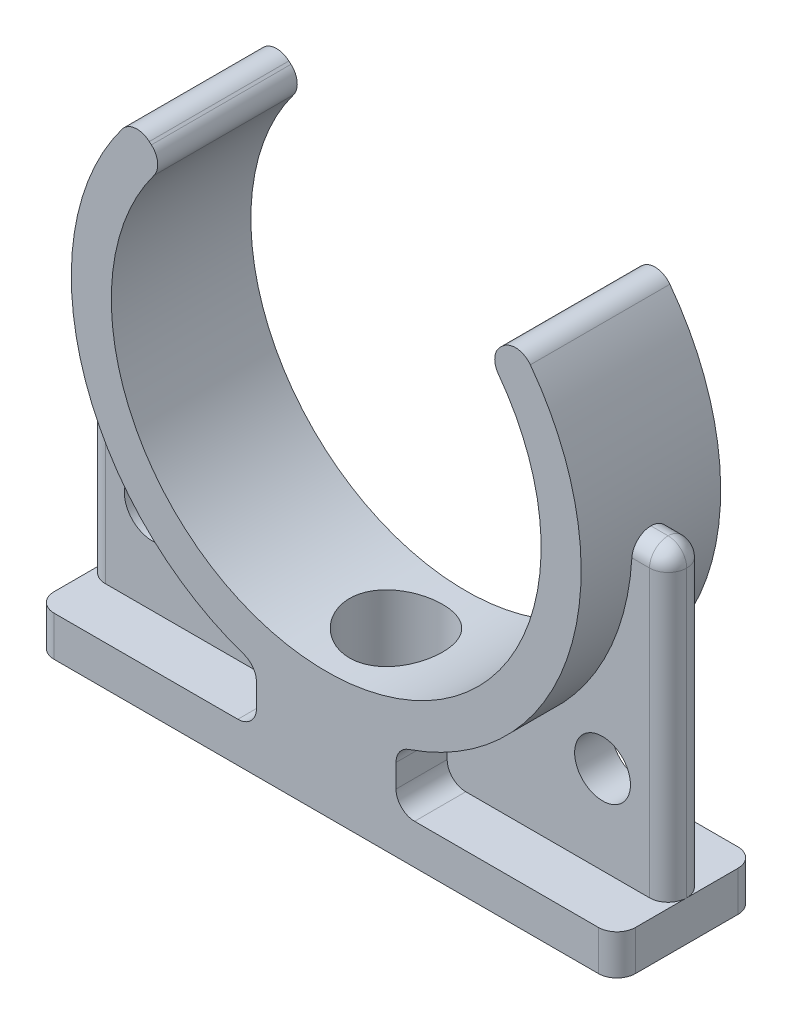
SolidWorks part; units mm, degrees
material "Delrin 2700 NC010, Low Viscosity Acetal Copolymer (SS)"
ref_plane "Front Plane" through (0, 0, 0) normal (0, 0, 1) x (1, 0, 0)
ref_plane "Top Plane" through (0, 0, 0) normal (0, 1, 0) x (1, 0, 0)
ref_plane "Right Plane" through (0, 0, 0) normal (1, 0, 0) x (0, 0, -1)
sketch "Sketch1" plane through (0, 0, 0) normal (0, 0, 1) x (1, 0, 0)
  line L0 (39.6875, 17.145) -> (39.6875, 0) construction
  line L1 (0, 0) -> (79.375, 0)
  line L2 (0, 0) -> (0, 46.99)
  line L3 (0, 46.99) -> (4.8932, 46.99)
  line L4 (79.375, 0) -> (79.375, 46.99)
  line L5 (0, 5.461) -> (30.1625, 5.461)
  line L6 (30.1625, 13.013) -> (30.1625, 5.461)
  line L7 (49.2125, 13.013) -> (49.2125, 5.461)
  line L8 (74.4818, 46.99) -> (79.375, 46.99)
  line L9 (49.2125, 5.461) -> (79.375, 5.461)
  line L10 (13.5513, 69.4559) -> (17.653, 65.8505)
  line L11 (65.8237, 69.4559) -> (61.722, 65.8505)
  circle A0 centre (8.9535, 17.526) radius 3.81
  circle A1 centre (70.4215, 17.526) radius 3.81
  arc A2 (17.653, 65.8505) -> (61.722, 65.8505) centre (39.6875, 46.482) ccw
  arc A3 (49.2125, 13.013) -> (65.8237, 69.4559) centre (39.6875, 46.482) ccw
  arc A4 (13.5513, 69.4559) -> (30.1625, 13.013) centre (39.6875, 46.482) ccw
  point P12 (0, 0)
  point P14 (10.3505, 46.482)
  point P15 (4.8895, 46.482)
  point P16 (39.6875, 17.145)
  point P17 (8.9535, 13.716)
  point P27 (17.653, 65.8505)
  point P28 (61.722, 65.8505)
  dimension "D3" = 61.468
  dimension "D4" = 7.62
  dimension "D5" = 58.674
  dimension "D8" = 13.716
  dimension "D1" = 79.375
  dimension "D2" = 46.99
  dimension "D6" = 5.461
  dimension "D7" = 17.145
  dimension "D9" = 5.461
  dimension "D10" = 19.05
  dimension "D11" = 44.069
extrude "Boss-Extrude1" add sketch "Sketch1" along normal mid plane 19.05 contours A2 L0 L1 L4 L9 L7 A3 L11 | L0 A2 L10 A4 L6 L5 L2 L1 region at (60.1684, 22.8572, 0) region at (19.2066, 22.8572, 0)
extrude "Boss-Extrude2" add sketch "Sketch1<3>" along direction (0, 0, 1) on the side of the normal mid plane 5.08 contours A4 L3 L2 L5 L6 A0 | A3 L7 L9 L4 L8 A1 region at (0.5133, 26.2255, 0) region at (64.2938, 5.9743, 0)
sketch "Sketch1<3>" plane through (0, 0, 0) normal (0, 0, 1) x (1, 0, 0) same geometry as "Sketch1"
fillet "Fillet1" radius 2.54 14 edges at (17.653, 65.8505, 0) (13.5513, 69.4559, 0) (65.8237, 69.4559, 0) (61.722, 65.8505, 0) (76.9284, 46.99, -2.54) (76.9284, 46.99, 2.54) (49.2125, 5.461, 6.0325) (49.2125, 13.013, 6.0325) (79.375, 26.2255, -2.54) (79.375, 26.2255, 2.54) (0, 2.7305, -9.525) (79.375, 2.7305, -9.525) (79.375, 2.7305, 9.525) (0, 2.7305, 9.525)
sketch "Sketch2" plane through (0, 0, 0) normal (0, -1, 0) x (1, 0, 0)
  circle A0 centre (39.6875, 0) radius 2.54
  dimension "D1" = 5.08
extrude "Cut-Extrude1" cut sketch "Sketch2" against normal through all
sketch "Sketch5" plane through (0, 0, 0) normal (0, -1, 0) x (1, 0, 0)
  circle A0 centre (39.6875, 0) radius 6.0325
  dimension "D1" = 12.065
ref_plane "Plane1" through (0, 19.05, 0) normal (0, -1, 0) x (-1, 0, 0)
sketch "Sketch7" plane through (0, 19.05, 0) normal (0, -1, 0) x (-1, 0, 0)
  circle A0 centre (-39.6875, 0) radius 6.35
  dimension "D1" = 12.7
extrude "Cut-Extrude2" cut sketch "Sketch7" along normal blind 18.415
fillet "Fillet2" radius 2.54 6 edges at (30.1625, 13.013, 6.0325) (30.1625, 5.461, 6.0325) (2.4466, 46.99, -2.54) (2.4466, 46.99, 2.54) (0, 26.2255, -2.54) (0, 26.2255, 2.54)
fillet "Fillet3" radius 2.54 4 edges at (30.1625, 5.461, -6.0325) (30.1625, 13.013, -6.0325) (49.2125, 5.461, -6.0325) (49.2125, 13.013, -6.0325)
